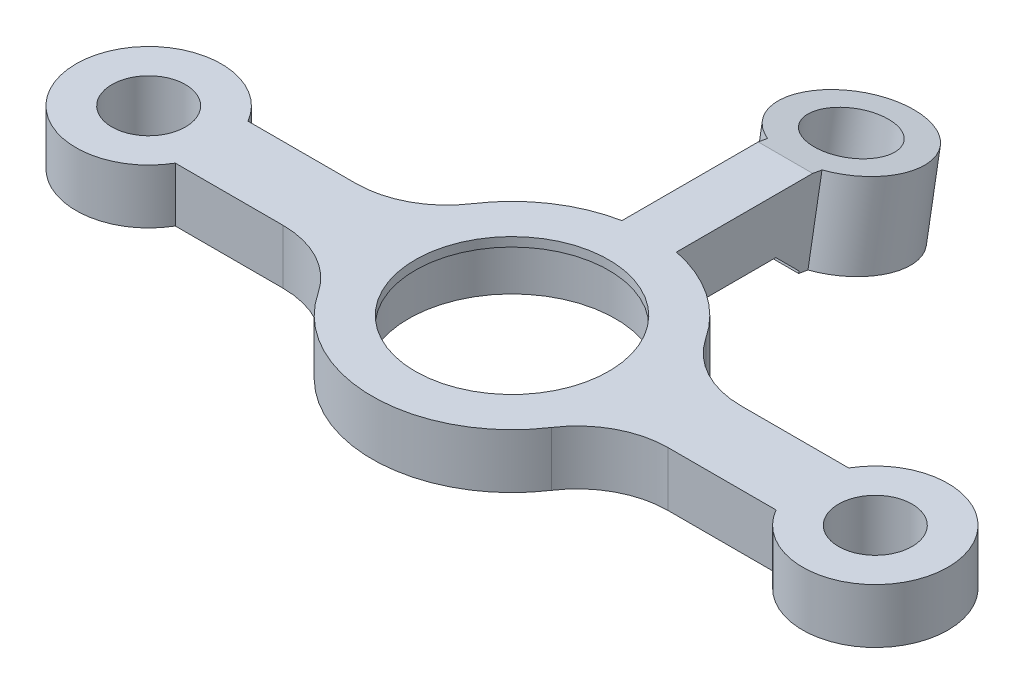
SolidWorks part; units mm, degrees
material "ABS"
ref_plane "Plano frontal" through (0, 0, 0) normal (0, 0, 1) x (1, 0, 0)
ref_plane "Plano superior" through (0, 0, 0) normal (0, 1, 0) x (1, 0, 0)
ref_plane "Plano direito" through (0, 0, 0) normal (1, 0, 0) x (0, 0, -1)
sketch "Esboço1" plane through (0, 0, 0) normal (0, 1, 0) x (1, 0, 0)
  line L0 (-40, 0) -> (40, 0) construction
  line L1 (-33.0718, 4) -> (-21.1934, 4)
  line L2 (-33.0718, -4) -> (-21.1934, -4)
  line L3 (21.1934, 4) -> (33.0718, 4)
  line L4 (21.1934, -4) -> (33.0718, -4)
  line L5 (-3, 15.105) -> (-3, 30.105)
  line L7 (3, 30.105) -> (3, 15.105)
  line L8 (0, 25.1417) -> (0, 0) construction
  line L9 (-3, 30.105) -> (3, 30.105)
  arc A0 (-33.0718, 4) -> (-33.0718, -4) centre (-40, 0) ccw
  arc A1 (33.0718, -4) -> (33.0718, 4) centre (40, 0) ccw
  circle A2 centre (40, 0) radius 4.05
  circle A3 centre (-40, 0) radius 4.05
  arc A4 (-12.8495, -8.4882) -> (12.8495, -8.4882) centre (0, 0) ccw
  arc A5 (12.8495, 8.4882) -> (3, 15.105) centre (0, 0) ccw
  circle A6 centre (0, 0) radius 11.4
  arc A7 (-12.8495, -8.4882) -> (-21.1934, -4) centre (-21.1934, -14) ccw
  arc A8 (21.1934, -4) -> (12.8495, -8.4882) centre (21.1934, -14) ccw
  arc A9 (21.1934, 4) -> (12.8495, 8.4882) centre (21.1934, 14) cw
  arc A10 (-12.8495, 8.4882) -> (-21.1934, 4) centre (-21.1934, 14) cw
  arc A11 (-3, 15.105) -> (-12.8495, 8.4882) centre (0, 0) ccw
  point P4 (0, 0)
  point P22 (14.8714, 4)
  dimension "D2" = 8.1
  dimension "D3" = 16
  dimension "D5" = 4
  dimension "D6" = 22.8
  dimension "D7" = 10
  dimension "D10" = 15
  dimension "D1" = 80
  dimension "D4" = 8
  dimension "D9" = 6
extrude "Ressalto-extrusão1" add sketch "Esboço1" along normal blind 6
sketch "Esboço2" plane through (0, 6, 0) normal (0, 1, 0) x (1, 0, 0)
  circle A0 centre (0, 0) radius 10.65
  circle A1 centre (0, 0) radius 11.4
  circle A2 centre (0, 0) radius 11.4 construction
  dimension "D1" = 0.75
extrude "Ressalto-extrusão2" add sketch "Esboço2" against normal blind 1
sketch "Esboço3" plane through (-3, 0, 0) normal (-1, 0, 0) x (0, 0, 1)
  line L0 (-30.105, 0) -> (-27.6405, -13.9766) construction
  line L1 (-30.105, 0) -> (-15.105, 0) construction
  dimension "D1" = 80
ref_plane "Plano1" through (0, 5.1483, -0.9078) normal (0, -0.9848, 0.1736) x (-1, 0, 0)
sketch "Esboço4" plane through (0, 5.1483, -0.9078) normal (0, -0.9848, 0.1736) x (-1, 0, 0)
  line L0 (-3, 29.6476) -> (3, 29.6476) construction
  line L1 (3, 28.6057) -> (-3, 28.6057)
  line L2 (-3, 14.8755) -> (-3, 29.6476) construction
  line L3 (-3, 28.6057) -> (-3, 29.6476)
  line L4 (3, 29.6476) -> (3, 28.6057)
  arc A0 (3, 29.6476) -> (-3, 29.6476) centre (0, 35.9722) ccw
  circle A1 centre (0, 35.9722) radius 4.15
  point P7 (0, 29.6476)
  dimension "D1" = 14
  dimension "D2" = 8.3
extrude "Ressalto-extrusão4" add sketch "Esboço4" against normal up to vertex (5.9088 mm away) and the other way blind 3 up to point (3, 6, -30.105)
chamfer "Chanfro1" distance 3 angle 45 1 edges at (0, 0, -29.047) first distance on face at (0, 0, 11.4)
